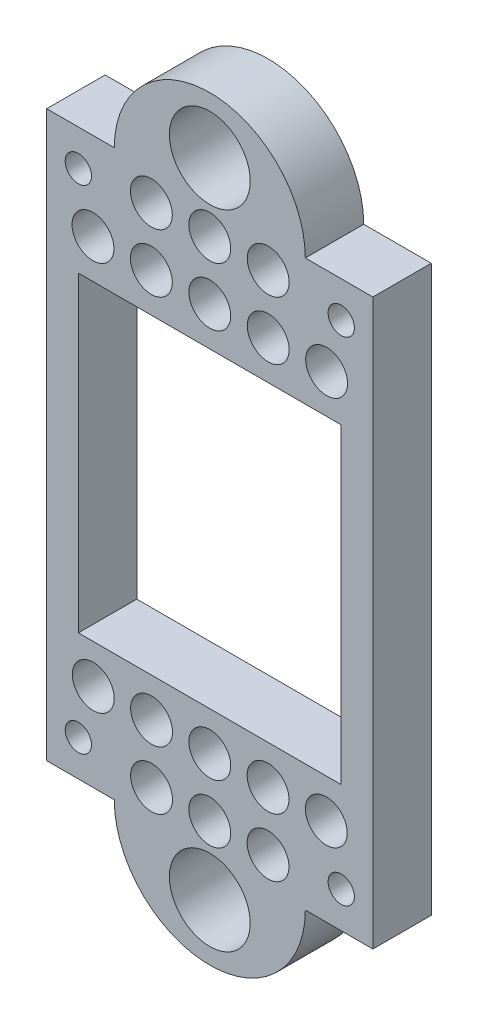
SolidWorks part; units mm, degrees
ref_plane "Front Plane" through (0, 0, 0) normal (0, 0, 1) x (1, 0, 0)
ref_plane "Top Plane" through (0, 0, 0) normal (0, 1, 0) x (1, 0, 0)
ref_plane "Right Plane" through (0, 0, 0) normal (1, 0, 0) x (0, 0, -1)
sketch "Sketch1" plane through (0, 0, 0) normal (0, 0, 1) x (1, 0, 0)
  line L0 (-13.5, -16) -> (13.5, -16)
  line L1 (-16.75, 29) -> (-9.8115, 29)
  line L2 (-16.75, 29) -> (-16.75, -29)
  line L3 (-16.75, -29) -> (-9.8115, -29)
  line L4 (16.75, 29) -> (16.75, -29)
  line L5 (-13.5, 16) -> (13.5, 16)
  line L6 (-13.5, 16) -> (-13.5, -16)
  line L8 (13.5, 16) -> (13.5, -16)
  line L14 (-19.5, 29.3) -> (19.5, 29.3) construction
  line L15 (-19.5, 29.3) -> (-19.5, -29.3) construction
  line L16 (-19.5, -29.3) -> (19.5, -29.3) construction
  line L17 (19.5, 29.3) -> (19.5, -29.3) construction
  line L20 (0, 0) -> (4.3335, 0) construction
  line L21 (9.8115, 29) -> (16.75, 29)
  line L22 (9.8115, -29) -> (16.75, -29)
  circle A2 centre (-13.5, 25.3) radius 1.35
  circle A4 centre (13.5, -25.3) radius 1.35
  circle A5 centre (-13.5, -25.3) radius 1.35
  circle A6 centre (13.5, 25.3) radius 1.35
  circle A8 centre (0, 33) radius 4.15
  circle A13 centre (0, -33) radius 4.15
  arc A16 (-9.8115, 29) -> (9.8115, 29) centre (0, 29) cw
  arc A17 (-9.8115, -29) -> (9.8115, -29) centre (0, -29) ccw
  point P8 (-9.2352, 29)
  point P10 (-16.75, 0)
  point P11 (0, 16)
  point P12 (-13.5, 0)
  point P13 (9.8115, 29)
  point P29 (19.5, 0)
  point P30 (0, 29.3)
  dimension "D8" = 2.7
  dimension "D22" = 8.3
  dimension "D23" = 4
  dimension "D1" = 27
  dimension "D2" = 33.5
  dimension "D3" = 58
  dimension "D4" = 32
  dimension "D9" = 58.6
  dimension "D10" = 39
  dimension "D11" = 6
  dimension "D12" = 4
  dimension "D13" = 4
  dimension "D14" = 6
  dimension "D15" = 6
  dimension "D16" = 6
  dimension "D17" = 4
  dimension "D18" = 4
extrude "Boss-Extrude1" add sketch "Sketch1" along normal blind 6
sketch "Sketch2" plane through (0, 0, 6) normal (0, 0, 1) x (1, 0, 0)
  line L3 (13.5, 16) -> (-13.5, 16) construction
  line L4 (-13.5, -16) -> (13.5, -16) construction
  circle A0 centre (-12, 20) radius 2.15
  circle A1 centre (-6, 20) radius 2.15
  circle A2 centre (0, 20) radius 2.15
  circle A3 centre (6, 20) radius 2.15
  circle A4 centre (12, 20) radius 2.15
  circle A5 centre (-6, 26) radius 2.15
  circle A6 centre (0, 26) radius 2.15
  circle A7 centre (6, 26) radius 2.15
  circle A8 centre (-11.9673, -20) radius 2.15
  circle A9 centre (-5.9837, -20) radius 2.15
  circle A10 centre (0, -20) radius 2.15
  circle A11 centre (5.9837, -20) radius 2.15
  circle A12 centre (11.9673, -20) radius 2.15
  circle A13 centre (-5.9837, -26) radius 2.15
  circle A14 centre (0, -26) radius 2.15
  circle A15 centre (5.9837, -26) radius 2.15
  dimension "D1" = 4.3
  dimension "D5" = 4.3
  dimension "D11" = 4.3
  dimension "D12" = 4.3
  dimension "D13" = 4.3
  dimension "D14" = 4.3
  dimension "D15" = 4.3
  dimension "D16" = 4.3
  dimension "D2" = 4
  dimension "D3" = 4
  dimension "D6" = 6
  dimension "D10" = 6
  dimension "D4" = 5
  dimension "D9" = 5
extrude "Cut-Extrude1" cut sketch "Sketch2" against normal blind 4.2
